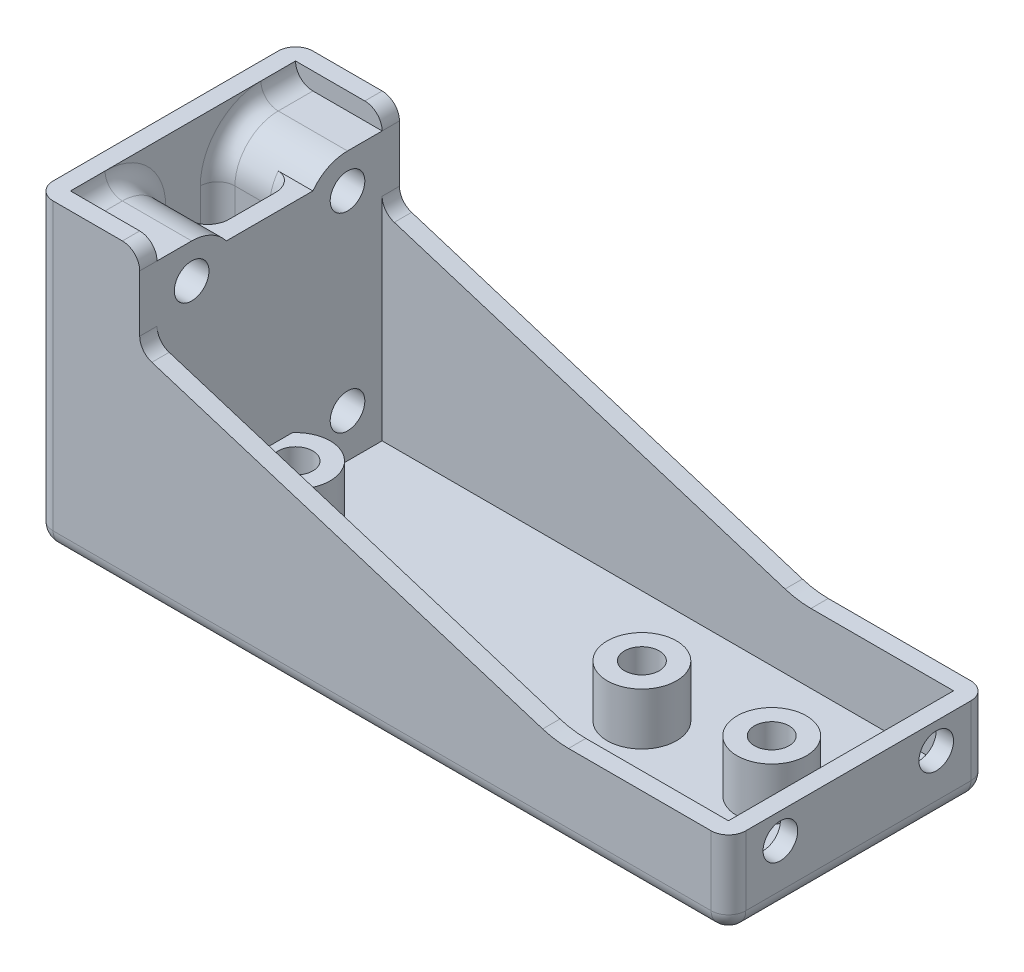
SolidWorks part; units mm, degrees
ref_plane "Front Plane" through (0, 0, 0) normal (0, 0, 1) x (1, 0, 0)
ref_plane "Top Plane" through (0, 0, 0) normal (0, 1, 0) x (1, 0, 0)
ref_plane "Right Plane" through (0, 0, 0) normal (1, 0, 0) x (0, 0, -1)
sketch "Sketch1" plane through (0, 0, 0) normal (0, 0, 1) x (1, 0, 0)
  line L0 (0, 35) -> (0, 0)
  line L1 (0, 0) -> (80, 0)
  line L2 (80, 0) -> (80, 10)
  line L3 (80, 10) -> (60, 10)
  line L4 (60, 10) -> (13.4035, 24.5614)
  line L5 (12, 26.4704) -> (12, 33)
  line L6 (10, 35) -> (0, 35)
  arc A1 (13.4035, 24.5614) -> (12, 26.4704) centre (14, 26.4704) cw
  arc A2 (12, 33) -> (10, 35) centre (10, 33) ccw
  point P10 (80, 0)
  point P13 (12, 25)
  point P16 (12, 35)
  dimension "D1" = 80
  dimension "D2" = 35
  dimension "D3" = 12
  dimension "D4" = 10
  dimension "D5" = 20
  dimension "D6" = 10
extrude "Boss-Extrude1" add sketch "Sketch1" along normal mid plane 30
fillet "Fillet2" radius 10 1 edges at (60, 10, 0)
fillet "Fillet3" radius 2 4 edges at (0, 17.5, -15) (0, 17.5, 15) (80, 5, -15) (80, 5, 15)
fillet "Fillet4" radius 2 8 edges at (0.5858, 0, 14.4142) (40, 0, 15) (79.4142, 0, 14.4142) (80, 0, 0) (79.4142, 0, -14.4142) (40, 0, -15) (0.5858, 0, -14.4142) (0, 0, 0)
shell "Shell1" thickness 2 removed face at (73.3134, 10, 0) removed face at (60.0261, 10.171, 0) removed face at (35.9734, 17.5083, 0) removed face at (12.5452, 25.4008, 0) removed face at (12, 29.7352, 0) removed face at (11.2071, 34.2071, 0) removed face at (3.8619, 35, 0)
sketch "Sketch2" plane through (0, 2, 0) normal (0, 1, 0) x (1, 0, 0)
  line L0 (0, 0) -> (70, 0) construction
  circle A0 centre (70, 0) radius 2
  circle A1 centre (55, 0) radius 2
  circle A2 centre (15, 0) radius 2
  point P7 (57.0648, 0)
  point P9 (16.6951, 0)
  dimension "D1" = 4
  dimension "D3" = 40
  dimension "D4" = 15
  dimension "D2" = 15
extrude "Cut-Extrude1" cut sketch "Sketch2" against normal through all
sketch "Sketch3" plane through (0, 2, 0) normal (0, 1, 0) x (1, 0, 0)
  circle A0 centre (70, 0) radius 2 construction
  circle A1 centre (15, 0) radius 2 construction
  circle A2 centre (55, 0) radius 2 construction
  circle A3 centre (70, 0) radius 2
  circle A4 centre (15, 0) radius 2
  circle A5 centre (55, 0) radius 2
  circle A6 centre (70, 0) radius 4
  circle A7 centre (55, 0) radius 4
  circle A8 centre (15, 0) radius 4
  dimension "D1" = 8
extrude "Boss-Extrude2" add sketch "Sketch3" along normal blind 6
sketch "Sketch4" plane through (12, 0, 0) normal (1, 0, 0) x (0, 0, -1)
  line L0 (4, 2) -> (-4, 2) construction
  line L1 (-13, 33) -> (13, 33)
  line L2 (-13, 33) -> (-13, 2)
  line L3 (-13, 2) -> (13, 2)
  line L4 (13, 33) -> (13, 2)
  point P5 (13, 33)
extrude "Boss-Extrude3" add sketch "Sketch4" against normal up to surface (10 mm away) up to face at (2, 18.5, 0)
sketch "Sketch5" plane through (0, 33, 0) normal (0, 1, 0) x (1, 0, 0)
  line L0 (2, -13) -> (2, 13) construction
  line L1 (2, -4) -> (10, -4)
  line L2 (2, -4) -> (2, 4)
  line L3 (2, 4) -> (10, 4)
  line L4 (10, -4) -> (10, 4)
  line L5 (0, 0) -> (15, 0) construction
  line L6 (12, 13) -> (12, -13) construction
  dimension "D1" = 8
  dimension "D2" = 2
extrude "Cut-Extrude2" cut sketch "Sketch5" against normal up to surface (31 mm away) up to face at (35.1667, 2, 0)
sketch "Sketch6" plane through (10, 0, 0) normal (-1, 0, 0) x (0, 0, 1)
  line L0 (4, 2) -> (4, 33) construction
  line L1 (-4, 33) -> (4, 33)
  line L2 (-4, 33) -> (-4, 31)
  line L3 (-4, 31) -> (4, 31)
  line L4 (4, 33) -> (4, 31)
  dimension "D1" = 2
extrude "Cut-Extrude3" cut sketch "Sketch6" against normal blind 6
fillet "Fillet5" radius 5 2 edges at (7, 33, -4) (7, 33, 4)
fillet "Fillet6" radius 2 11 edges at (2, 33, -11) (2, 31.5355, -5.4645) (10, 29.5811, -4.2566) (2, 33, 11) (2, 31.5355, 5.4645) (2, 15, -4) (10, 15, -4) (2, 15, 4) (10, 29.5811, 4.2566) (6, 2, 4) (10, 15, 4)
sketch "Sketch7" plane through (0, 0, 0) normal (-1, 0, 0) x (0, 0, 1)
  line L0 (0, 35) -> (0, 0) construction
  line L1 (13, 35) -> (-13, 35) construction
  circle A0 centre (-9, 29) radius 2
  circle A1 centre (-9, 7) radius 2
  circle A2 centre (9, 7) radius 2
  circle A3 centre (9, 29) radius 2
  point P9 (0, 0)
  dimension "D1" = 4
  dimension "D2" = 9
  dimension "D3" = 6
  dimension "D4" = 22
extrude "Cut-Extrude4" cut sketch "Sketch7" against normal through all
sketch "Sketch8" plane through (0, 0, 0) normal (-1, 0, 0) x (0, 0, 1)
  line L0 (0, 35) -> (0, 0) construction
  line L1 (13, 35) -> (-13, 35) construction
  line L2 (-9, 29) -> (-9, 7) construction
  line L3 (-9, 13) -> (-9, 23) construction
  line L4 (-11.5, 13) -> (-11.5, 23)
  line L5 (-6.5, 13) -> (-6.5, 23)
  line L6 (9, 13) -> (9, 23) construction
  line L7 (11.5, 13) -> (11.5, 23)
  line L8 (6.5, 13) -> (6.5, 23)
  line L9 (9, 29) -> (9, 7) construction
  arc A0 (-11.5, 13) -> (-6.5, 13) centre (-9, 13) ccw
  arc A1 (-6.5, 23) -> (-11.5, 23) centre (-9, 23) ccw
  arc A2 (11.5, 13) -> (6.5, 13) centre (9, 13) cw
  arc A3 (6.5, 23) -> (11.5, 23) centre (9, 23) cw
  point P11 (-9, 18)
  point P18 (9, 18)
  dimension "D1" = 2.5
  dimension "D2" = 10
extrude "Cut-Extrude6" cut sketch "Sketch8" against normal offset from surface (10 mm away) 2 up to face at (12, 29, 11)
